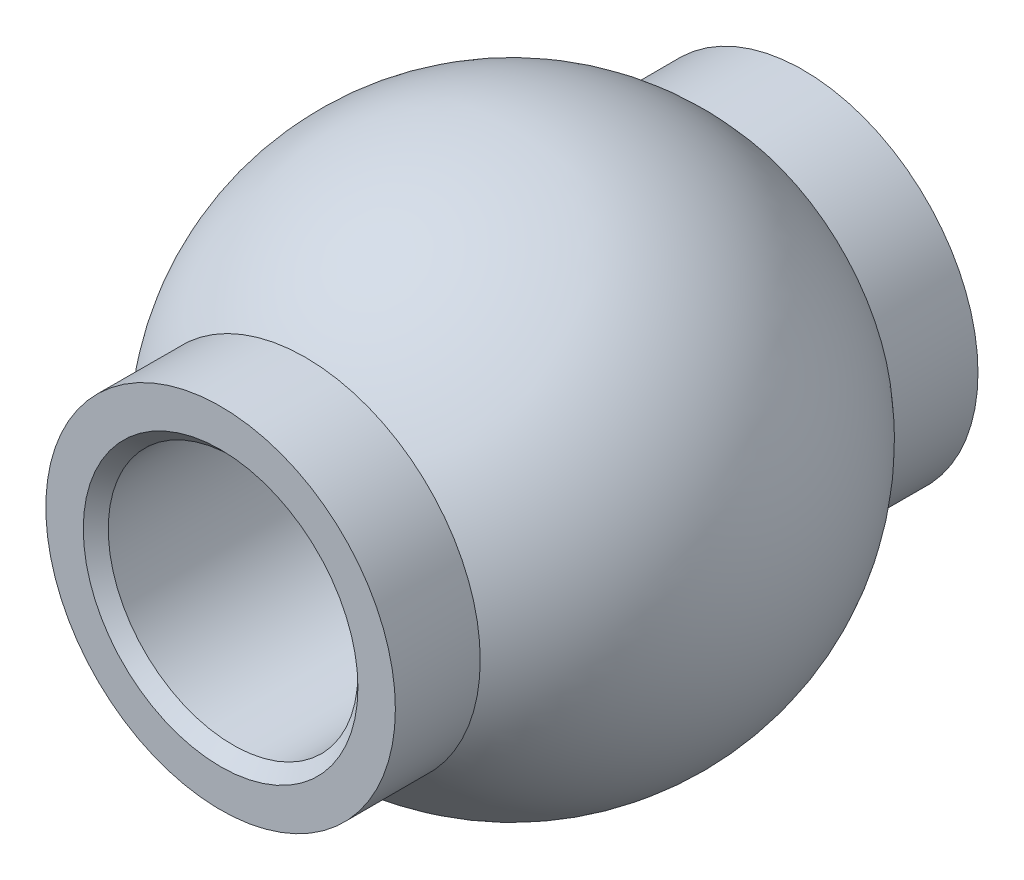
SolidWorks part; units mm, degrees
ref_plane "Front" through (0, 0, 0) normal (0, 0, 1) x (1, 0, 0)
ref_plane "Top" through (0, 0, 0) normal (0, 1, 0) x (1, 0, 0)
ref_plane "Right" through (0, 0, 0) normal (1, 0, 0) x (0, 0, -1)
sketch "Sketch1" plane through (0, 0, 0) normal (0, 0, 1) x (1, 0, 0)
  line L0 (0, 0) -> (0, -34.925)
  line L1 (0, -34.925) -> (4.7625, -34.925)
  line L2 (4.7625, -34.925) -> (4.7625, 0)
  line L3 (4.7625, 0) -> (0, 0)
  line L5 (0, 33.3375) -> (0, 0) construction
  line L6 (0, 33.3375) -> (14.2875, 33.3375) construction
  line L7 (14.2875, 33.3375) -> (14.2875, 19.05) construction
  line L8 (-4.7625, -34.925) -> (-4.7625, 0) construction
  line L9 (3.8092, -34.925) -> (4.7625, -33.9717)
  line L10 (4.8772, -34.8588) -> (4.8772, -35.918) construction
  line L11 (4.8772, -35.918) -> (3.9599, -35.3884) construction
  line L12 (3.9599, -35.3884) -> (4.8772, -34.8588) construction
  line L13 (3.9599, -35.3884) -> (4.0745, -35.3884) construction
  line L14 (4.8772, -35.3884) -> (4.7625, -35.3884) construction
  line L15 (4.0745, -35.4546) -> (4.0745, -35.3222) construction
  line L16 (4.7625, -35.8518) -> (4.7625, -34.925) construction
  line L17 (4.8198, -35.8849) -> (4.8198, -34.8919) construction
  arc A0 (8.5725, 7.62) -> (0, 33.3375) centre (0, 19.05) ccw construction
  circle A1 centre (0, 19.05) radius 4.7625 construction
  circle A2 centre (0, 19.05) radius 10.3187 construction
  circle A3 centre (0, 19.05) radius 10.8347 construction
  arc A4 (4.7625, 0) -> (8.5725, 7.62) centre (14.2875, 0) cw construction
  point P16 (-4.7625, -31.2179)
  point P28 (4.0745, -35.3884)
  point P31 (4.7625, -35.3884)
  point P34 (4.8198, -35.3884)
  dimension "Ball Dia" = 20.6375
  dimension "D1" = 21.6694
  dimension "ID" = 9.525
  dimension "D2" = 3.7071
  dimension "D3" = 45
  dimension "D4" = 0.9533
  dimension "Pitch" = 1.0592
  dimension "D5" = 0.1324
  dimension "Thread Size" = 9.525
  dimension "Overall Width" = 28.575
  dimension "Shank Thread Length" = 34.925
  dimension "Shank Center Length" = 53.975
sketch "Sketch2" plane through (0, 0, 0) normal (1, 0, 0) x (0, 0, -1)
  line L0 (-11.1125, 19.05) -> (11.1125, 19.05)
  line L2 (0, 25.7175) -> (0, 12.3825)
  line L3 (0, 23.8125) -> (0, 14.2875) construction
  line L4 (11.1125, 25.7175) -> (-11.1125, 25.7175)
  line L5 (11.1125, 23.8125) -> (-11.1125, 23.8125)
  line L6 (11.1125, 14.2875) -> (-11.1125, 14.2875)
  line L7 (11.1125, 12.3825) -> (-11.1125, 12.3825)
  line L8 (0, 19.05) -> (-11.1125, 24.8348) construction
  line L9 (0, 19.05) -> (-11.1125, 13.2652) construction
  point P0 (0, 23.8125)
  point P4 (0, 19.05)
  point P9 (0, 19.05)
  point P10 (0, 14.2875)
  point P18 (0, 23.8125)
  point P21 (0, 25.7175)
  point P24 (0, 14.2875)
  point P27 (0, 12.3825)
  dimension "D1" = 13.335
  dimension "Overall Thickness" = 22.225
  dimension "Maximum Ball Swivel" = 55
sketch "Sketch13" plane through (0, 0, 0) normal (0, 0, 1) x (1, 0, 0)
  line L0 (3.8092, -34.925) -> (4.7625, -33.9717) construction
  line L1 (3.8092, -34.925) -> (4.7625, -33.9717)
  line L4 (0, 0) -> (0, -34.925)
  line L5 (0, -34.925) -> (4.7625, -34.925)
  line L6 (4.7625, -34.925) -> (4.7625, 0)
  line L7 (4.7625, 0) -> (0, 0)
  line L8 (0, 0) -> (0, -34.925)
  line L9 (0, -34.925) -> (3.8092, -34.925)
  line L10 (4.7625, -33.9717) -> (4.7625, 0)
  line L11 (4.7625, 0) -> (0, 0)
  dimension "D1" = 0
revolve "Revolve4" [suppressed] add sketch "Sketch13" angle 360 about L8
sketch "Sketch4" plane through (0, 0, 0) normal (0, 0, 1) x (1, 0, 0)
  line L0 (4.7625, 0) -> (0, 0) construction
  line L1 (0, 8.7312) -> (0, 0)
  line L2 (0, 33.3375) -> (0, 0) construction
  line L3 (4.7625, 0) -> (0, 0)
  line L5 (0, 33.3375) -> (0, 29.3687)
  line L6 (0, 33.3375) -> (0, 35.8775) construction
  arc A0 (8.5725, 7.62) -> (0, 33.3375) centre (0, 19.05) ccw construction
  arc A1 (8.5725, 7.62) -> (0, 33.3375) centre (0, 19.05) ccw
  arc A2 (8.5725, 7.62) -> (4.7625, 0) centre (14.2875, 0) ccw construction
  arc A3 (8.5725, 7.62) -> (4.7625, 0) centre (14.2875, 0) ccw
  circle A4 centre (0, 19.05) radius 10.3187 construction
  arc A5 (0, 8.7312) -> (0, 29.3687) centre (0, 19.05) ccw
  dimension "D1" = 2.54
revolve "Revolve2" [suppressed] add sketch "Sketch4" angle 360 about L6
sketch "Sketch5" [suppressed] plane through (0, 0, 0) normal (1, 0, 0) x (0, 0, -1)
  line L0 (4.5641, 33.3375) -> (14.2875, 33.3375)
  line L1 (-4.5641, 33.3375) -> (4.5641, 33.3375) construction
  line L2 (-4.5641, 33.3375) -> (-4.5641, 1.8256)
  line L3 (-4.7625, 0) -> (4.7625, 0) construction
  line L4 (4.5641, 33.3375) -> (4.5641, 1.8256)
  line L5 (14.2875, 33.3375) -> (14.2875, 0)
  line L6 (14.2875, 0) -> (4.7625, 0)
  line L7 (-4.7625, 0) -> (-14.2875, 0)
  line L8 (-14.2875, 0) -> (-14.2875, 33.3375)
  line L9 (-14.2875, 33.3375) -> (-4.5641, 33.3375)
  line L10 (4.7625, 0) -> (4.5641, 1.8256)
  line L11 (-4.7625, 0) -> (-4.5641, 1.8256)
  line L12 (-4.5641, 1.8256) -> (4.5641, 1.8256) construction
  line L13 (0, 0) -> (0, 1.8256) construction
  arc A0 (8.5725, 7.62) -> (-8.5725, 7.62) centre (0, 19.05) ccw construction
  dimension "F" = 9.1281
  dimension "D2" = 1.8256
  dimension "D1" = 9.525
extrude "Cut-Extrude1" [suppressed] cut sketch "Sketch5" against normal through all and the other way through all
sketch "Sketch7" plane through (0, 0, 0) normal (0, 0, 1) x (1, 0, 0)
  line L0 (0, 29.3687) -> (0, 8.7312)
  line L1 (0, 33.3375) -> (0, 0) construction
  line L2 (0, 0) -> (0, 8.7312) construction
  arc A0 (0, 8.7312) -> (0, 29.3687) centre (0, 19.05) ccw
  circle A1 centre (0, 19.05) radius 10.3187 construction
revolve "Revolve3" add sketch "Sketch7" angle 360 about L2
sketch "Sketch10" plane through (0, 0, 0) normal (0, 0, 1) x (1, 0, 0)
  circle A0 centre (0, 19.05) radius 4.7625 construction
  circle A1 centre (0, 19.05) radius 4.7625
extrude "Cut-Extrude4" cut sketch "Sketch10" against normal through all and the other way through all
sketch "Sketch12" plane through (0, 0, 0) normal (0, 0, 1) x (1, 0, 0)
  circle A0 centre (0, 19.05) radius 6.6675
  circle A1 centre (0, 19.05) radius 4.7625 construction
  circle A2 centre (0, 19.05) radius 4.7625
  dimension "D1" = 13.335
extrude "Extrude1" add sketch "Sketch12" against normal up to vertex (11.1125 mm away) and the other way up to vertex (11.1125 mm away) up to point (0, 19.05, -11.1125) other way up to point (0, 19.05, 11.1125)
chamfer "Chamfer1" distance 0.4762 angle 45 2 edges at (4.7625, 19.05, -11.1125) (4.7625, 19.05, 11.1125)
sketch "Sketch11" [suppressed] plane through (0, 0, 0) normal (1, 0, 0) x (0, 0, -1)
  line L5 (0, 19.05) -> (0.0074, 19.05) construction
  line L9 (-4.5641, 32.5889) -> (-4.5641, 7.62) construction
  line L10 (4.5641, 7.62) -> (4.5641, 32.5889) construction
  arc A0 (-7.8753, 12.3825) -> (7.8753, 12.3825) centre (0, 19.05) ccw construction
  arc A1 (7.8753, 25.7175) -> (-7.8753, 25.7175) centre (0, 19.05) ccw construction
  arc A2 (-4.5641, 9.7955) -> (4.5641, 9.7955) centre (0, 19.05) ccw
  arc A3 (4.5641, 28.3045) -> (-4.5641, 28.3045) centre (0, 19.05) ccw
sketch "Sketch14" [suppressed] plane through (0, -34.925, 0) normal (0, -1, 0) x (1, 0, 0)
  circle A0 centre (0, 0) radius 4.7625
curve "Helix/Spiral1" [suppressed] pitch 1.0592 height 35.9842 turns 33.9736
split "Split1" [suppressed] bodies to split 122 118 115
sketch "Sketch15" plane through (0, 0, 0) normal (0, 0, 1) x (1, 0, 0)
  line L0 (4.0745, -35.3222) -> (4.8198, -34.8919)
  line L1 (4.8198, -34.8919) -> (4.8198, -35.8849)
  line L2 (4.8198, -35.8849) -> (4.0745, -35.4546)
  line L3 (4.0745, -35.4546) -> (4.0745, -35.3222)
sweep "Cut-Sweep1" [suppressed] cut profiles "Sketch15" path "Helix/Spiral1"
sketch "Sketch16" plane through (0, 0, 0) normal (0, 1, 0) x (1, 0, 0)
  circle A0 centre (0, 0) radius 4.7625
extrude "Boss-Extrude1" [suppressed] add sketch "Sketch16" against normal blind 2.54 draft 45
sketch "Sketch17" plane through (0, 0, 0) normal (0, 0, 1) x (1, 0, 0)
  point P1 (0, 19.05)
  point P2 (0, 0)
equation "\"D1@Sketch1\"=\"Ball Dia@Sketch1\"*1.05"
equation "\"D1@Chamfer1\" = \"ID@Sketch1\" / 20"
equation "\"D1@Sketch5\"= \"Thread Size@Sketch1\""
equation "\"D2@Sketch5\"=\"F@Sketch5\"/5"
equation "\"D1@Sketch12\"= \"ID@Sketch1\" * 1.4"
equation "\"D5@Sketch1\"=\"Pitch@Sketch1\"/8"
equation "\"D4@Sketch1\"=\"Pitch@Sketch1\"*.9"
equation "\"D3@Helix/Spiral1\"= \"Shank Thread Length@Sketch1\" + \"Pitch@Sketch1\""
equation "\"D4@Helix/Spiral1\"=\"Pitch@Sketch1\""
equation "\"D2@Sketch1\"=\"Pitch@Sketch1\"*3.5"
equation "\"D1@Sketch2\"=\"ID@Sketch1\"*1.4"
